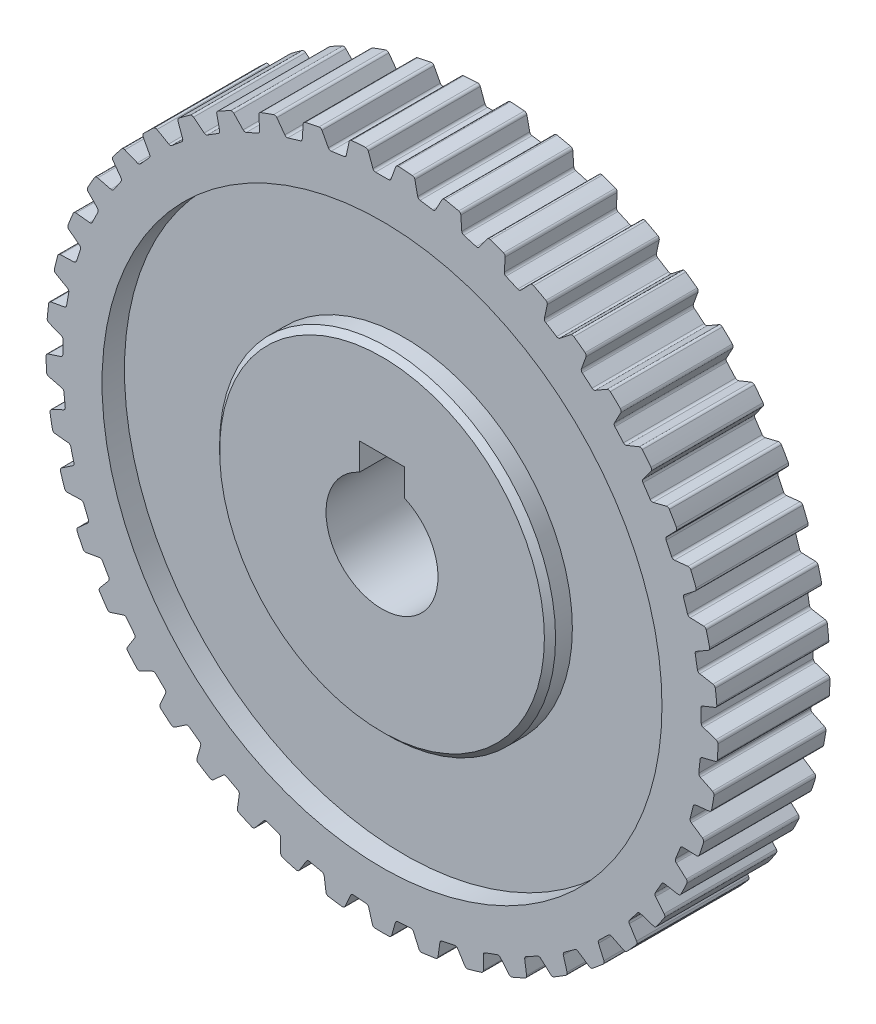
SolidWorks part; units mm, degrees
ref_plane "Front Plane" through (0, 0, 0) normal (0, 0, 1) x (1, 0, 0)
ref_plane "Top Plane" through (0, 0, 0) normal (0, 1, 0) x (1, 0, 0)
ref_plane "Right Plane" through (0, 0, 0) normal (1, 0, 0) x (0, 0, -1)
sketch "Sketch1" plane through (0, 0, 0) normal (0, 0, 1) x (1, 0, 0)
  line L1 (-2, 7) -> (2, 7)
  line L2 (-2, 7) -> (-2, 4.5826)
  line L4 (2, 7) -> (2, 4.5826)
  circle A0 centre (0, 0) radius 30
  arc A1 (-2, 4.5826) -> (2, 4.5826) centre (0, 0) ccw
  point P4 (0, 5)
  dimension "D1" = 60
  dimension "D2" = 10
  dimension "D3" = 4
  dimension "D4" = 7
  dimension "D5" = 2.4174
extrude "Boss-Extrude2" add sketch "Sketch1" along normal mid plane 10
sketch "Sketch2" plane through (0, 0, 5) normal (0, 0, 1) x (1, 0, 0)
  line L0 (0, 30) -> (0, 0) construction
  line L1 (-0.75, 28.5) -> (0.75, 28.5)
  line L2 (0.75, 28.5) -> (1.2859, 29.9724)
  line L3 (-0.75, 28.5) -> (-1.2859, 29.9724)
  circle A0 centre (0, 0) radius 30 construction
  arc A1 (-1.2859, 29.9724) -> (1.2859, 29.9724) centre (0, 27.8285) cw
  point P10 (0, 28.5)
  dimension "D3" = 2.5
  dimension "D1" = 0.75
  dimension "D2" = 20
  dimension "D4" = 28.5
extrude "Cut-Extrude1" cut sketch "Sketch2" against normal through all
pattern_circular "CirPattern1" count 45 over 360 about axis through (0, 0, 5) along (0, 0, 1) of "Cut-Extrude1"
sketch "Sketch3" plane through (0, 0, 5) normal (0, 0, 1) x (1, 0, 0)
  circle A0 centre (0, 0) radius 25
  circle A1 centre (0, 0) radius 15
  dimension "D1" = 30
  dimension "D2" = 50
extrude "Cut-Extrude2" cut sketch "Sketch3" against normal blind 2
mirror "Mirror1" about plane through (0, 0, 0) normal (0, 0, 1) of "Cut-Extrude2"
chamfer "Chamfer1" distance 0.5 angle 45 2 edges at (15, 0, 5) (15, 0, -5)
fillet "Fillet1" radius 0.25 180 edges at (28.4223, -2.2332, 0) (29.9427, -1.8541, 0) (29.999, -0.2391, 0) (28.5088, 0.2451, 0) (28.4565, 1.7442, 0) (29.9093, 2.3312, 0) (29.7404, 3.9383, 0) (28.1973, 4.2104, 0) (27.9368, 5.6876, 0) (29.2938, 6.471, 0) (28.9028, 8.039, 0) (27.3369, 8.0937, 0) (26.8733, 9.5203, 0) (28.1081, 10.485, 0) (27.5027, 11.9833, 0) (25.9444, 11.8195, 0) (25.2869, 13.1677, 0) (26.3753, 14.2948, 0) (25.5673, 15.6943, 0) (24.047, 15.3152, 0) (23.2082, 16.5588, 0) (24.1292, 17.8264, 0) (23.1343, 19.0998, 0) (21.6815, 18.5129, 0) (20.6778, 19.6276, 0) (21.4134, 21.0111, 0) (20.251, 22.1336, 0) (18.894, 21.3502, 0) (17.7449, 22.3144, 0) (18.2808, 23.7868, 0) (16.9735, 24.7366, 0) (15.7387, 23.7719, 0) (14.4667, 24.5668, 0) (14.7924, 26.0995, 0) (13.3656, 26.8581, 0) (12.2772, 25.731, 0) (10.9068, 26.3411, 0) (11.0161, 27.9042, 0) (9.4976, 28.4569, 0) (8.5766, 27.1892, 0) (7.1347, 27.6027, 0) (7.0254, 29.1658, 0) (5.4448, 29.5018, 0) (4.7091, 28.1183, 0) (3.2237, 28.327, 0) (2.898, 29.8597, 0) (1.2859, 29.9724, 0) (0.75, 28.5, 0) (-0.75, 28.5, 0) (-1.2859, 29.9724, 0) (-2.898, 29.8597, 0) (-3.2237, 28.327, 0) (-4.7091, 28.1183, 0) (-7.0254, 29.1658, 0) (-7.1347, 27.6027, 0) (-8.5766, 27.1892, 0) (-9.4976, 28.4569, 0) (-11.0161, 27.9042, 0) (-10.9068, 26.3411, 0) (-12.2772, 25.731, 0) (-13.3656, 26.8581, 0) (-14.7924, 26.0995, 0) (-14.4667, 24.5668, 0) (-15.7387, 23.7719, 0) (-16.9735, 24.7366, 0) (-18.2808, 23.7868, 0) (-17.7449, 22.3144, 0) (-18.894, 21.3502, 0) (-20.251, 22.1336, 0) (-21.4134, 21.0111, 0) (-20.6778, 19.6276, 0) (-21.6815, 18.5129, 0) (-23.1343, 19.0998, 0) (-24.1292, 17.8264, 0) (-23.2082, 16.5588, 0) (-24.047, 15.3152, 0) (-25.5673, 15.6943, 0) (-26.3753, 14.2948, 0) (-25.2869, 13.1677, 0) (-25.9444, 11.8195, 0) (-27.5027, 11.9833, 0) (-28.1081, 10.485, 0) (-26.8733, 9.5203, 0) (-27.3369, 8.0937, 0) (-28.9028, 8.039, 0) (-29.2938, 6.471, 0) (-27.9368, 5.6876, 0) (-28.1973, 4.2104, 0) (-29.7404, 3.9383, 0) (-29.9093, 2.3312, 0) (-28.4565, 1.7442, 0) (-28.5088, 0.2451, 0) (-29.999, -0.2391, 0) (-29.9427, -1.8541, 0) (-28.4223, -2.2332, 0) (-28.2655, -3.725, 0) (-29.6738, -4.4118, 0) (-29.3932, -6.0033, 0) (-27.8349, -6.1671, 0) (-27.472, -7.6225, 0) (-28.771, -8.4987, 0) (-28.2717, -10.0356, 0) (-26.7057, -9.9809, 0) (-26.1438, -11.3717, 0) (-27.3082, -12.4202, 0) (-26.5998, -13.8726, 0) (-25.0567, -13.6005, 0) (-24.3067, -14.8995, 0) (-25.3139, -16.0999, 0) (-24.4103, -17.4396, 0) (-22.9201, -16.9553, 0) (-21.9966, -18.1374, 0) (-22.8269, -19.4662, 0) (-21.7456, -20.6671, 0) (-20.3373, -19.9802, 0) (-19.2583, -21.0222, 0) (-19.8956, -22.4536, 0) (-18.6577, -23.4924, 0) (-17.3586, -22.6161, 0) (-16.1451, -23.4978, 0) (-16.577, -25.004, 0) (-15.2066, -25.8604, 0) (-14.0422, -24.8119, 0) (-12.7177, -25.5161, 0) (-12.9358, -27.0678, 0) (-11.4595, -27.7251, 0) (-10.4523, -26.5247, 0) (-9.0428, -27.0378, 0) (-9.0428, -28.6047, 0) (-7.4894, -29.0501, 0) (-6.6591, -27.7213, 0) (-5.1919, -28.0331, 0) (-4.9738, -29.5848, 0) (-3.3736, -29.8097, 0) (-2.7362, -28.3783, 0) (-1.2399, -28.4829, 0) (-0.808, -29.9891, 0) (0.808, -29.9891, 0) (1.2399, -28.4829, 0) (2.7362, -28.3783, 0) (3.3736, -29.8097, 0) (4.9738, -29.5848, 0) (5.1919, -28.0331, 0) (6.6591, -27.7213, 0) (7.4894, -29.0501, 0) (9.0428, -28.6047, 0) (9.0428, -27.0378, 0) (10.4523, -26.5247, 0) (11.4595, -27.7251, 0) (12.9358, -27.0678, 0) (12.7177, -25.5161, 0) (14.0422, -24.8119, 0) (15.2066, -25.8604, 0) (16.577, -25.004, 0) (16.1451, -23.4978, 0) (17.3586, -22.6161, 0) (18.6577, -23.4924, 0) (19.8956, -22.4536, 0) (19.2583, -21.0222, 0) (20.3373, -19.9802, 0) (21.7456, -20.6671, 0) (22.8269, -19.4662, 0) (21.9966, -18.1374, 0) (22.9201, -16.9553, 0) (24.4103, -17.4396, 0) (25.3139, -16.0999, 0) (24.3067, -14.8995, 0) (25.0567, -13.6005, 0) (26.5998, -13.8726, 0) (27.3082, -12.4202, 0) (26.1438, -11.3717, 0) (26.7057, -9.9809, 0) (28.2717, -10.0356, 0) (28.771, -8.4987, 0) (27.472, -7.6225, 0) (27.8349, -6.1671, 0) (29.3932, -6.0033, 0) (29.6738, -4.4118, 0) (28.2655, -3.725, 0) (-5.4448, 29.5018, 0)
